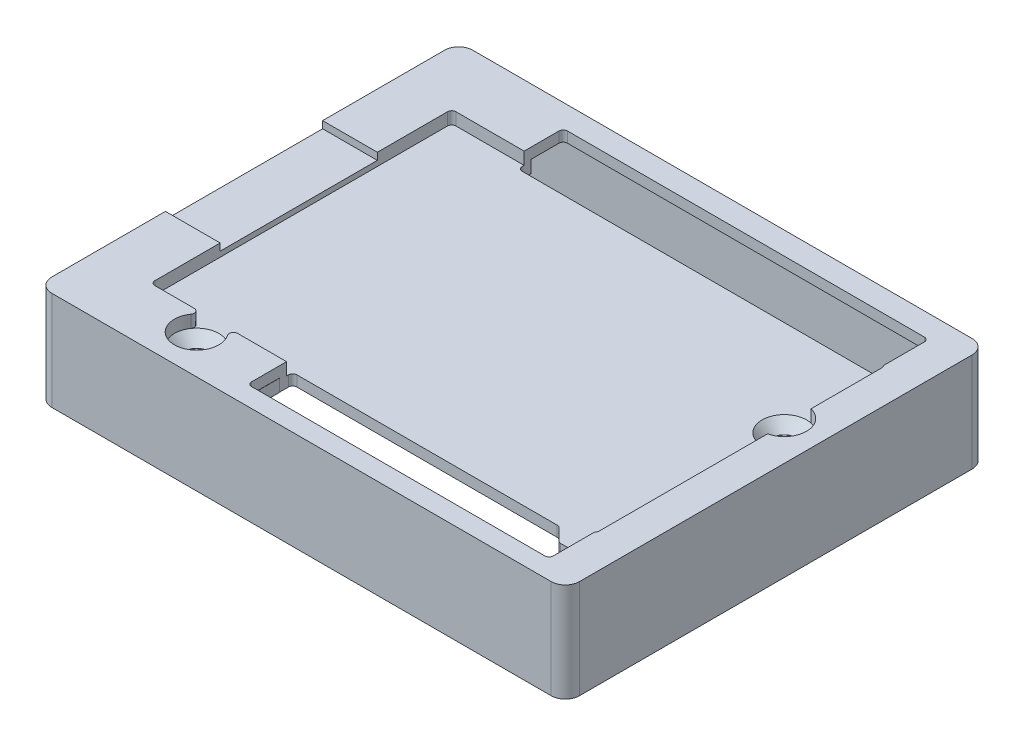
SolidWorks part; units mm, degrees
ref_plane "Front Plane" through (0, 0, 0) normal (0, 0, 1) x (1, 0, 0)
ref_plane "Top Plane" through (0, 0, 0) normal (0, 1, 0) x (1, 0, 0)
ref_plane "Right Plane" through (0, 0, 0) normal (1, 0, 0) x (0, 0, -1)
ref_plane "PCB_TOP" through (0, 1.5, 0) normal (0, 1, 0) x (1, 0, 0)
ref_plane "Max misc component height" through (0, 10.25, 0) normal (0, 1, 0) x (1, 0, 0)
sketch "Board Outline" plane through (0, 0, 0) normal (0, 1, 0) x (1, 0, 0)
  line L1 (0, 0) -> (68.7, 0)
  line L2 (0, 0) -> (0, 53.6)
  line L3 (0, 53.6) -> (68.7, 53.6)
  line L4 (68.7, 0) -> (68.7, 53.6)
  dimension "D1" = 68.7
  dimension "D2" = 53.6
sketch "Sketch2" plane through (0, 0, 0) normal (0, 1, 0) x (1, 0, 0)
  line L4 (69.7, 54.6) -> (-1, 54.6)
  line L5 (-1, 54.6) -> (-1, -1)
  line L6 (-1, -1) -> (69.7, -1)
  line L7 (69.7, -1) -> (69.7, 54.6)
  line L8 (-3, 56.6) -> (-3, -3)
  line L9 (-3, -3) -> (71.7, -3)
  line L10 (71.7, -3) -> (71.7, 56.6)
  line L11 (71.7, 56.6) -> (-3, 56.6)
  line L12 (-3, 56.6) -> (-3, -3)
  line L13 (-3, -3) -> (71.7, -3)
  line L14 (71.7, -3) -> (71.7, 56.6)
  line L15 (71.7, 56.6) -> (-3, 56.6)
  dimension "D1" = 3
  dimension "D2" = 2
extrude "walls" add sketch "Sketch2" along normal blind 12.5 from offset 1.5
sketch "Sketch3" plane through (0, 0, 0) normal (1, 0, 0) x (0, 0, -1)
  line L1 (-3, 14) -> (56.6, 14)
  line L2 (-3, 14) -> (-3, 15.5)
  line L3 (-3, 15.5) -> (56.6, 15.5)
  line L4 (56.6, 14) -> (56.6, 15.5)
  dimension "D1" = 1.5
extrude "Boss-Extrude2" add sketch "Sketch3" along normal up to surface (71.7 mm away) from surface up to face at (71.7, 7.75, -26.8) starting at face at (-3, 7.75, -26.8)
sketch "Sketch4" plane through (0, 1.5, 0) normal (0, 1, 0) x (1, 0, 0)
  line L12 (-8.8, 31) -> (11.6, 31)
  line L13 (11.6, 31) -> (11.6, 47.1)
  line L14 (11.6, 47.1) -> (-8.8, 47.1)
  line L15 (-8.8, 47.1) -> (-8.8, 31)
extrude "Cut-Extrude1" cut sketch "Sketch4" along normal blind 12
sketch "Sketch5" plane through (0, 1.5, 0) normal (0, 1, 0) x (1, 0, 0)
  line L12 (-5.4, 2.25) -> (12.85, 2.25)
  line L13 (12.85, 2.25) -> (12.85, 15.25)
  line L14 (12.85, 15.25) -> (-5.4, 15.25)
  line L15 (-5.4, 15.25) -> (-5.4, 2.25)
extrude "Cut-Extrude2" cut sketch "Sketch5" along normal blind 12.1
sketch "Sketch6" plane through (0, 1.5, 0) normal (0, 1, 0) x (1, 0, 0)
  line L12 (15, 47) -> (66.73, 47)
  line L13 (66.73, 47) -> (66.73, 53.4)
  line L14 (66.73, 53.4) -> (15, 53.4)
  line L15 (15, 53.4) -> (15, 47)
  line L24 (24, -0.3) -> (66.7, -0.3)
  line L25 (66.7, -0.3) -> (66.7, 6.1)
  line L26 (66.7, 6.1) -> (24, 6.1)
  line L27 (24, 6.1) -> (24, -0.3)
extrude "Cut-Extrude3" cut sketch "Sketch6" along normal through all
sketch "RFID chip outline" plane through (0, 15.5, 0) normal (0, 1, 0) x (1, 0, 0)
  line L0 (40.865, 47) -> (40.865, 6.1) construction
  line L1 (4.75, 5.235) -> (66.9, 5.235)
  line L2 (4.75, 5.235) -> (4.75, 47.865)
  line L3 (4.75, 47.865) -> (66.9, 47.865)
  line L4 (66.9, 5.235) -> (66.9, 47.865)
  line L5 (15, 47) -> (66.73, 47) construction
  line L6 (66.7, 6.1) -> (24, 6.1) construction
  line L7 (66.9, 37.2822) -> (1.8, 37.2822) construction
  line L8 (71.7, 56.6) -> (-3, 56.6) construction
  point P10 (40.865, 26.55)
  point P11 (34.35, 37.2822)
  point P12 (4.75, 26.55)
  point P18 (34.35, 56.6)
  dimension "D1" = 62.15
  dimension "D2" = 42.63
  dimension "D3" = 65.1
sketch "Sketch13" plane through (0, 10.25, 0) normal (0, 1, 0) x (1, 0, 0)
  line L4 (15, 53.4) -> (15, 47) construction
  line L5 (15, 47) -> (66.73, 47) construction
  line L6 (66.73, 47) -> (66.73, 53.4) construction
  line L7 (66.7, -0.3) -> (66.7, 6.1) construction
  line L8 (3.75, 4.235) -> (67.9, 4.235)
  line L9 (67.9, 4.235) -> (67.9, 48.865)
  line L10 (67.9, 48.865) -> (3.75, 48.865)
  line L11 (3.75, 48.865) -> (3.75, 4.235)
  line L12 (3.75, 4.235) -> (24, 4.235)
  line L13 (67.9, 4.235) -> (67.9, 48.865)
  line L14 (67.9, 48.865) -> (66.73, 48.865)
  line L15 (3.75, 48.865) -> (3.75, 4.235)
  line L16 (24, 6.1) -> (24, -0.3) construction
  line L17 (66.7, 6.1) -> (24, 6.1) construction
  line L18 (15, 48.865) -> (15, 47)
  line L19 (15, 47) -> (66.73, 47)
  line L20 (66.73, 47) -> (66.73, 48.865)
  line L21 (66.7, 4.235) -> (66.7, 6.1)
  line L22 (24, 6.1) -> (24, 4.235)
  line L23 (66.7, 6.1) -> (24, 6.1)
  line L24 (15, 48.865) -> (3.75, 48.865)
  line L25 (66.7, 4.235) -> (67.9, 4.235)
  dimension "D1" = 1
extrude "Boss-Extrude5" add sketch "Sketch13" along normal up to surface (5.25 mm away) from offset 2 up to face at (45.35, 15.5, -2.9)
sketch "Sketch15" plane through (0, 15.5, 0) normal (0, 1, 0) x (1, 0, 0)
  line L0 (4.75, 5.235) -> (66.9, 5.235) construction
  line L1 (66.9, 5.235) -> (66.9, 47.865) construction
  line L2 (4.75, 47.865) -> (66.9, 47.865) construction
  line L3 (4.75, 5.235) -> (4.75, 47.865) construction
  line L4 (4.75, 5.235) -> (24, 5.235)
  line L5 (66.9, 6.1) -> (66.9, 47)
  line L6 (4.75, 47.865) -> (15, 47.865)
  line L7 (4.75, 5.235) -> (4.75, 47.865)
  line L9 (15, 47) -> (66.73, 47) construction
  line L10 (15, 53.4) -> (15, 47) construction
  line L12 (24, 6.1) -> (24, -0.3) construction
  line L13 (66.7, 6.1) -> (24, 6.1) construction
  line L15 (15, 47) -> (66.9, 47)
  line L16 (15, 47.865) -> (15, 47)
  line L18 (24, 6.1) -> (24, 5.235)
  line L19 (66.9, 6.1) -> (24, 6.1)
extrude "Cut-Extrude6" cut sketch "Sketch15" against normal blind 1.75
sketch "Sketch16" plane through (0, 15.5, 0) normal (0, 1, 0) x (1, 0, 0)
  line L0 (-3, 15.085) -> (-3, 37.335)
  line L8 (-3, 56.6) -> (-3, -3) construction
  line L13 (-3, 15.085) -> (9.95, 15.085)
  line L14 (9.95, 15.085) -> (9.95, 37.335)
  line L15 (9.95, 37.335) -> (-3, 37.335)
extrude "Cut-Extrude7" cut sketch "Sketch16" against normal blind 1
sketch "Sketch45" plane through (0, 13.75, 0) normal (0, 1, 0) x (1, 0, 0)
  line L1 (24, 6.1) -> (66.7, 6.1) construction
  line L2 (63.7, 4.1) -> (66.7, 4.1)
  line L3 (66.7, -0.3) -> (66.7, 6.1) construction
  line L4 (66.7, 4.1) -> (66.7, 6.1)
  line L5 (66.7, 6.1) -> (61.7, 6.1)
  line L6 (63.7, 4.1) -> (61.7, 6.1)
  dimension "D1" = 2
  dimension "D2" = 45
  dimension "D3" = 3
extrude "Hole padding" add sketch "Sketch45" against normal up to surface (1.5 mm away) up to face at (40.68, 12.25, -26.55)
sketch "Sketch43" plane through (0, 14, 0) normal (0, -1, 0) x (1, 0, 0)
  line L1 (67.9, -48.865) -> (67.9, -4.235)
  line L2 (67.9, -4.1) -> (69.7, -4.1)
  line L4 (69.7, -4.1) -> (69.7, -48.865)
  line L12 (63.7, -4.1) -> (66.7, -4.1) construction
  line L14 (67.9, -48.865) -> (69.7, -48.865)
  line L15 (69.7, 1) -> (69.7, -54.6) construction
  line L18 (66.7, -4.1) -> (67.9, -4.1)
  line L19 (66.7, -4.1) -> (66.7, -4.235)
  line L20 (66.7, -4.235) -> (67.9, -4.235)
extrude "Roof fill-in" add sketch "Sketch43" along normal up to surface (1.75 mm away) up to face at (43.8257, 12.25, -23.3429)
fillet "Fillet2" radius 2 4 edges at (-3, 8.5, 3) (71.7, 8.5, -56.6) (71.7, 8.5, 3) (-3, 8.5, -56.6)
sketch "Sketch18" plane through (0, 10.25, 0) normal (0, 1, 0) x (1, 0, 0)
  line L0 (11.6, 47.1) -> (-8.8, 47.1) construction
  line L1 (11.6, 31) -> (11.6, 47.1) construction
  line L2 (-8.8, 31) -> (11.6, 31) construction
  line L3 (-8.8, 47.1) -> (-8.8, 31) construction
  line L4 (11.6, 47.1) -> (-8.8, 47.1)
  line L5 (11.6, 31) -> (11.6, 47.1)
  line L6 (-8.8, 31) -> (11.6, 31)
  line L7 (-8.8, 47.1) -> (-8.8, 31)
  line L8 (12.85, 15.25) -> (-5.4, 15.25) construction
  line L9 (12.85, 2.25) -> (12.85, 15.25) construction
  line L10 (-5.4, 2.25) -> (12.85, 2.25) construction
  line L11 (-5.4, 15.25) -> (-5.4, 2.25) construction
  line L12 (12.85, 15.25) -> (-5.4, 15.25)
  line L13 (12.85, 2.25) -> (12.85, 15.25)
  line L14 (-5.4, 2.25) -> (12.85, 2.25)
  line L15 (-5.4, 15.25) -> (-5.4, 2.25)
extrude "Cut-Extrude9" cut sketch "Sketch18" along normal blind 1 from surface contours L4 L7 L6 L5 | L12 L15 L14 L13 starting at face at (40.3133, 12.25, -26.5275)
sketch "Sketch47" plane through (0, 14, 0) normal (0, -1, 0) x (1, 0, 0)
  line L1 (3.7782, -4.235) -> (11.8469, -4.235)
  line L2 (3.7782, -4.235) -> (3.7782, 1)
  line L3 (3.7782, 1) -> (24.0282, 1)
  line L4 (24.0282, -4.235) -> (24.0282, 1)
  line L6 (11.8469, -4.235) -> (11.8469, -5.0375)
  line L7 (11.8469, -5.0375) -> (12.85, -5.0375)
  line L8 (12.85, -5.0375) -> (12.85, -4.235)
  line L9 (12.85, -4.235) -> (24.0282, -4.235)
extrude "Roof fill in 2" add sketch "Sketch47" along normal up to surface (1.75 mm away) up to face at (30.0089, 12.25, -28.0572)
sketch "Sketch31" plane through (0, 13.75, 0) normal (0, 1, 0) x (1, 0, 0)
  circle A1 centre (66.2, 33.5) radius 1.5
  circle A3 centre (66, 7.5) radius 1.5
sketch "Sketch34" plane through (0, 13.75, 0) normal (0, 1, 0) x (1, 0, 0)
  circle A0 centre (66.2, 33.5) radius 3.15
  circle A3 centre (14, 2.5) radius 3.15
  dimension "D1" = 6.3
  dimension "D2" = 6.3
hole_wizard "CSK for M3 Flat Head Machine Screw8" positions "3DSketch12" profile "Sketch42" countersink size "M3" standard "ANSI Metric"
sketch3d "3DSketch12"
  point P0 (66.2, 13.75, -33.5)
  point P7 (14, 13.75, -2.5)
sketch "Sketch42" plane through (66.2, 13.75, -33.5) normal (1, 0, 0) x (0, 0, 1)
  line L0 (0, 0) -> (0, 8.5215)
  line L1 (0, 8.5215) -> (1.7, 7.5)
  line L2 (1.7, 7.5) -> (1.7, 1.45)
  line L3 (1.7, 1.45) -> (3.15, 0)
  line L5 (3.15, 0) -> (0, 0)
  line L6 (-1.7, 1.45) -> (-3.15, 0) construction
  line L10 (0, 8.5215) -> (-1.7, 7.5) construction
  line L11 (0, -6.35) -> (0, 107.95) construction
  dimension "Hole Dia." = 3.4
  dimension "Hole Depth" = 7.5
  dimension "Near C'Sink Dia." = 6.3
  dimension "Near C'Sink Angle" = 90
  dimension "Drill Angle" = 118
sketch "Sketch46" plane through (0, 13.75, 0) normal (0, 1, 0) x (1, 0, 0)
  circle A2 centre (66.2, 33.5) radius 3.15 construction
  circle A3 centre (66.2, 33.5) radius 3.15
  circle A4 centre (14, 2.5) radius 3.15 construction
  circle A5 centre (14, 2.5) radius 3.15
extrude "Hole clearance" cut sketch "Sketch46" along normal up to next
fillet "Fillet3" radius 0.6 27 edges at (69.7, 7.75, 1) (-1, 7.75, 1) (-1, 7.75, -54.6) (69.7, 7.75, -54.6) (12.85, 12.75, -15.25) (11.6, 12.75, -47.1) (11.6, 12.75, -31) (66.9, 14.625, -6.1) (66.9, 14.625, -47) (4.75, 14.625, -47.865) (4.75, 14.625, -5.235) (12.4372, 14.625, -5.235) (15.5628, 14.625, -5.235) (24, 13, -6.1) (66.7, 14.75, 0.3) (24, 14.75, 0.3) (15, 14.75, -53.4) (66.73, 13, -47) (66.73, 14.75, -53.4) (15, 13, -47) (11.8469, 12.75, -4.235) (12.85, 12.75, -5.0375) (63.7, 13, -4.1) (61.7, 13, -6.1) (3.7782, 13.125, 1) (69.7, 13.125, -4.1) (69.7, 13.125, -48.865)
